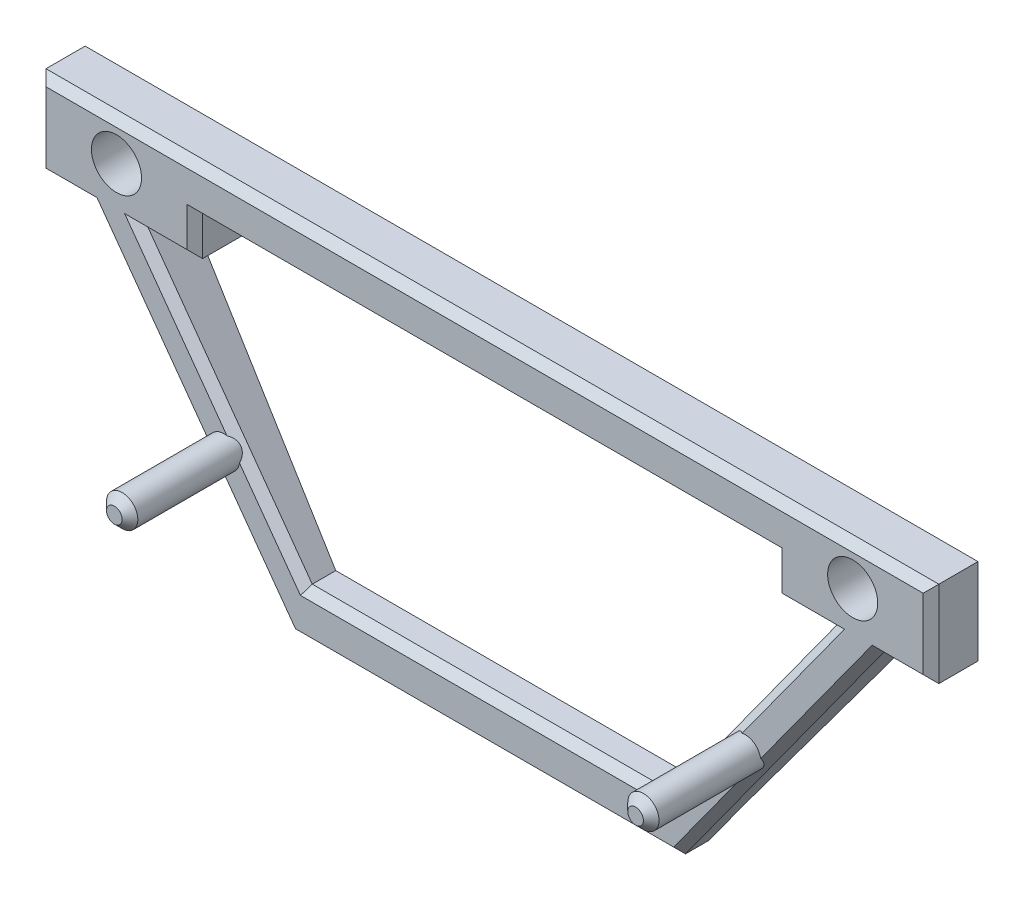
SolidWorks part; units mm, degrees
ref_plane "Ebene vorne" through (0, 0, 0) normal (0, 0, 1) x (1, 0, 0)
ref_plane "Ebene oben" through (0, 0, 0) normal (0, 1, 0) x (1, 0, 0)
ref_plane "Ebene rechts" through (0, 0, 0) normal (1, 0, 0) x (0, 0, -1)
sketch "Skizze1" plane through (0, 0, 0) normal (0, 0, 1) x (1, 0, 0)
  line L0 (0, 0) -> (0, 46.9928) construction
  line L3 (28.5, 17.5) -> (28.5, 23)
  line L5 (18.5, 20) -> (18.5, 17.5)
  line L13 (18.5, 17.5) -> (22, 17.5)
  line L14 (28.5, 17.5) -> (25, 17.5)
  line L15 (22, 17.5) -> (11.5, 3)
  line L16 (25, 17.5) -> (12.3276, 0)
  line L17 (11.5, 3) -> (-11.5, 3)
  line L18 (12.3276, 0) -> (-12.3276, 0)
  line L19 (-25, 17.5) -> (-12.3276, 0)
  line L20 (-22, 17.5) -> (-11.5, 3)
  line L21 (-28.5, 17.5) -> (-25, 17.5)
  line L22 (-18.5, 17.5) -> (-22, 17.5)
  line L23 (-18.5, 20) -> (-18.5, 17.5)
  line L24 (-28.5, 23) -> (28.5, 23)
  line L25 (-28.5, 17.5) -> (-28.5, 23)
  line L26 (22.5, 18.75) -> (22.5, 4.6099) construction
  line L28 (-18.5, 20) -> (18.5, 20)
  point P9 (0, 3)
  point P12 (0, 3)
  point P26 (28.5, 20.25)
  dimension "D1" = 23
  dimension "D2" = 57
  dimension "D3" = 5.5
  dimension "D4" = 3
  dimension "D5" = 3
  dimension "D6" = 3.5
  dimension "D7" = 10
  dimension "D8" = 3
  dimension "D9" = 23
extrude "Aufsatz-Linear austragen1" add sketch "Skizze1" along normal blind 3
sketch "Skizze3" plane through (0, 0, 3) normal (0, 0, 1) x (1, 0, 0)
  line L0 (0, 0) -> (0, 62.4514) construction
  line L1 (23.5, 17.5) -> (23.5, 34.1584) construction
  line L2 (25, 17.5) -> (28.5, 17.5) construction
  line L3 (28.5, 17.5) -> (28.5, 23) construction
  line L5 (-23.5, 17.5) -> (-23.5, 34.1584) construction
  circle A0 centre (23.5, 20.5) radius 1.6
  circle A1 centre (-23.5, 20.5) radius 1.6
  dimension "D2" = 3.2
  dimension "D1" = 5
  dimension "D3" = 3
extrude "Bohrungen" cut sketch "Skizze3" against normal through all
sketch "Skizze4" plane through (28.5, 0, 0) normal (1, 0, 0) x (0, 0, -1)
  line L1 (0, 17.5) -> (-1, 3)
  line L6 (-1, 3) -> (-1, 0)
  line L7 (-3, 0) -> (0, 0) construction
  line L8 (-1, 0) -> (0, 0)
  line L9 (0, 0) -> (0, 17.5)
  dimension "D1" = 1
  dimension "D2" = 3
extrude "Dicken_anpassung" cut sketch "Skizze4" against normal through all
sketch "Skizze5" plane through (0, 0, 3) normal (0, 0, 1) x (1, 0, 0)
  line L0 (0, 0) -> (0, 27.2221) construction
  line L2 (12.3276, 0) -> (25, 17.5) construction
  line L4 (28.5, 23) -> (-28.5, 23) construction
  circle A0 centre (16.6391, 8) radius 1
  circle A2 centre (-16.6391, 8) radius 1
  point P6 (0, 0)
  dimension "D2" = 2
  dimension "D1" = 15
  dimension "D4" = 1.2
extrude "Akkuhalterungen" add sketch "Skizze5" along normal blind 7
chamfer "Fase1" distance 0.5 angle 45 18 edges at (16.75, 10.25, 3) (20.25, 17.5, 3) (18.5, 18.75, 3) (0, 20, 3) (-18.5, 18.75, 3) (-20.25, 17.5, 3) (-16.75, 10.25, 3) (0, 3, 3) (-28.5, 20.25, 3) (0, 23, 3) (28.5, 20.25, 3) (26.75, 17.5, 3) (18.6638, 8.75, 3) (0, 0, 3) (-18.6638, 8.75, 3) (-26.75, 17.5, 3) (-17.6391, 8, 10) (17.6391, 8, 10)
